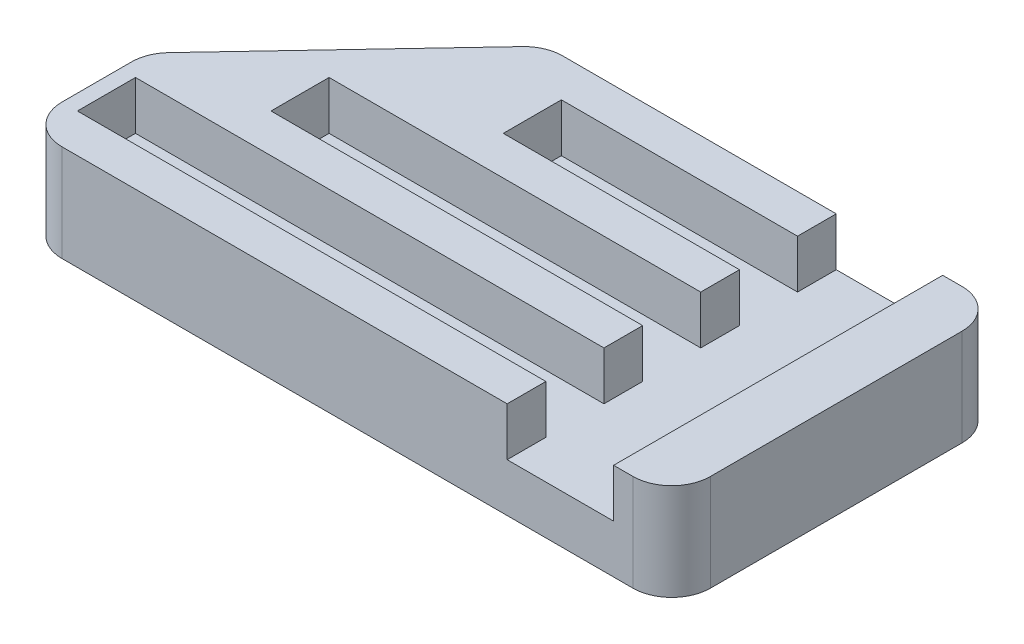
SolidWorks part; units mm, degrees
ref_plane "Спереди" through (0, 0, 0) normal (0, 0, 1) x (1, 0, 0)
ref_plane "Сверху" through (0, 0, 0) normal (0, 1, 0) x (1, 0, 0)
ref_plane "Справа" through (0, 0, 0) normal (1, 0, 0) x (0, 0, -1)
sketch "Эскиз1" plane through (0, 0, 0) normal (0, 1, 0) x (1, 0, 0)
  line L0 (0, 0) -> (0, 17) construction
  line L1 (0, 17) -> (5.5, 17)
  line L2 (5.5, 17) -> (5.5, 0)
  line L3 (5.5, 0) -> (0, 0)
  line L5 (0, 17) -> (-15, 17)
  line L6 (5.5, 17) -> (8.5, 17)
  line L7 (5.5, 17) -> (5.5, 0)
  line L8 (5.5, 0) -> (8.5, 0)
  line L9 (8.5, 17) -> (8.5, 0)
  line L10 (0, 0) -> (-25, 0)
  line L11 (-25, 0) -> (-25, 6.3905)
  line L12 (0, 0) -> (0, 2)
  line L13 (0, 2) -> (-24.2, 2)
  line L14 (-24.2, 2) -> (-24.2, 5)
  line L15 (-24.2, 5) -> (0, 5)
  line L16 (0, 5) -> (0, 7)
  line L17 (0, 7) -> (-19.2, 7)
  line L18 (-19.2, 7) -> (-19.2, 10)
  line L19 (-19.2, 10) -> (0, 10)
  line L20 (0, 10) -> (0, 12)
  line L21 (0, 12) -> (-12.2, 12)
  line L22 (-12.2, 12) -> (-12.2, 15)
  line L23 (-12.2, 15) -> (0, 15)
  line L24 (0, 15) -> (0, 17)
  line L25 (-25, 6.3905) -> (-15, 17)
  dimension "D1" = 17
  dimension "D2" = 5.5
  dimension "D3" = 3
  dimension "D4" = 2
  dimension "D5" = 2
  dimension "D6" = 2
  dimension "D7" = 3
  dimension "D8" = 3
  dimension "D9" = 2
  dimension "D10" = 12.2
  dimension "D11" = 19.2
  dimension "D12" = 24.2
  dimension "D13" = 25
  dimension "D14" = 15
extrude "Бобышка-Вытянуть1" add sketch "Эскиз1" against normal blind 2.5 contours L0 L12 L3 L2 L1 L24 L20 L16 | L13 L0 L15 L14 | L17 L0 L19 L18 | L21 L0 L23 L22 | L23 L24 L5 L11 L10 L12 L13 L14 L15 L16 L17 L18 L19 L20 L21 L22 | L9 L6 L2 L8 region at (-12.5, 0, -0.3023) region at (2.75, 0, -8.5) region at (-12.1, 0, -3.5) region at (7, 0, -8.5) region at (-9.6, 0, -8.5) region at (-6.1, 0, -13.5)
extrude "Бобышка-Вытянуть2" add sketch "Эскиз1<3>" along normal blind 2.5 contours L23 L24 L5 L11 L10 L12 L13 L14 L15 L16 L17 L18 L19 L20 L21 L22 | L9 L6 L2 L8 region at (-0.3023, 0, -16) region at (7, 0, -8.5)
sketch "Эскиз1<3>" plane through (0, 0, 0) normal (0, 1, 0) x (1, 0, 0) same geometry as "Эскиз1"
fillet "Скругление1" radius 2 5 edges at (8.5, 0, 0) (8.5, 0, -17) (-25, 0, 0) (-15, 0, -17) (-25, 0, -6.3905)
